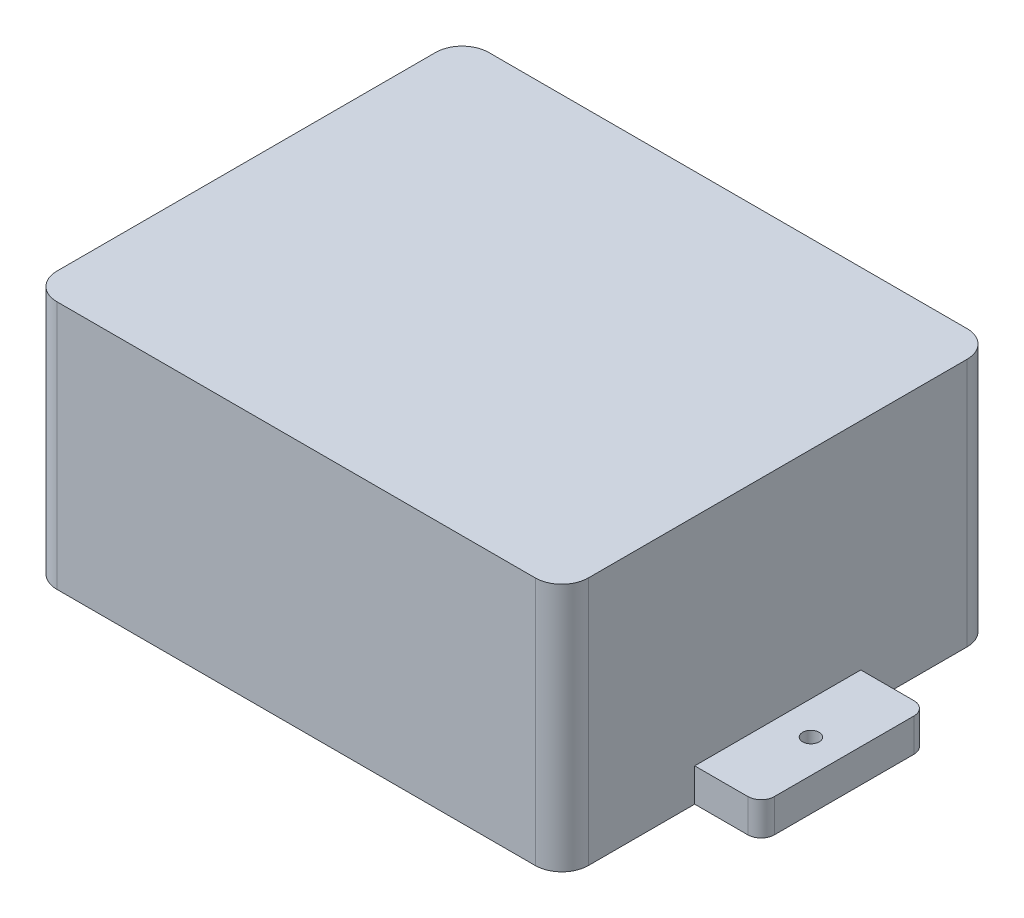
SolidWorks part; units mm, degrees
ref_plane "Front Plane" through (0, 0, 0) normal (0, 0, 1) x (1, 0, 0)
ref_plane "Top Plane" through (0, 0, 0) normal (0, 1, 0) x (1, 0, 0)
ref_plane "Right Plane" through (0, 0, 0) normal (1, 0, 0) x (0, 0, -1)
sketch "Sketch2" plane through (0, 0, 0) normal (0, 1, 0) x (1, 0, 0)
  line L0 (-50.8, 0) -> (50.8, 0) construction
  line L1 (0, -41.275) -> (0, 41.275) construction
  line L3 (-50.8, 41.275) -> (50.8, 41.275)
  line L4 (-50.8, 41.275) -> (-50.8, -41.275)
  line L5 (-50.8, -41.275) -> (50.8, -41.275)
  line L6 (50.8, 41.275) -> (50.8, -41.275)
  point P4 (0, 0)
  point P8 (0, 0)
  dimension "D1" = 82.55
  dimension "D2" = 101.6
  dimension "D3" = 50.8
  dimension "D4" = 41.275
extrude "Boss-Extrude1" add sketch "Sketch2" along normal blind 47.625 contours L4 L5 L6 L3
fillet "Fillet1" radius 5.08 4 edges at (50.8, 23.8125, 41.275) (50.8, 23.8125, -41.275) (-50.8, 23.8125, 41.275) (-50.8, 23.8125, -41.275)
sketch "Sketch3" plane through (0, 0, 0) normal (0, 1, 0) x (1, 0, 0)
  line L0 (50.8, -15.875) -> (63.5, -15.875)
  line L1 (50.8, 36.195) -> (50.8, -36.195) construction
  line L2 (50.8, 15.875) -> (63.5, 15.875)
  line L3 (-45.72, -41.275) -> (45.72, -41.275) construction
  line L4 (-45.72, 41.275) -> (45.72, 41.275) construction
  line L5 (63.5, 15.875) -> (63.5, -15.875)
  line L6 (50.8, 15.875) -> (50.8, -15.875)
  dimension "D1" = 25.4
  dimension "D2" = 25.4
  dimension "D3" = 12.7
sketch "Sketch4" plane through (0, 0, 0) normal (0, 1, 0) x (1, 0, 0)
  line L0 (-50.8, -15.875) -> (-63.5, -15.875)
  line L1 (-50.8, 36.195) -> (-50.8, -36.195) construction
  line L2 (-50.8, 15.875) -> (-63.5, 15.875)
  line L3 (-45.72, 41.275) -> (45.72, 41.275) construction
  line L4 (-45.72, -41.275) -> (45.72, -41.275) construction
  line L5 (-63.5, 15.875) -> (-63.5, -15.875)
  line L6 (-50.8, 15.875) -> (-50.8, -15.875)
  dimension "D1" = 25.4
  dimension "D2" = 25.4
  dimension "D3" = 12.7
extrude "Boss-Extrude2" add sketch "Sketch4" along normal blind 6.35 contours L5 L0 L6 L2
extrude "Boss-Extrude3" add sketch "Sketch3" along normal blind 6.35
fillet "Fillet2" radius 2.54 4 edges at (-63.5, 3.175, 15.875) (-63.5, 3.175, -15.875) (63.5, 3.175, -15.875) (63.5, 3.175, 15.875)
sketch "Sketch5" plane through (0, 0, 0) normal (0, 1, 0) x (1, 0, 0)
  line L0 (15.875, 41.275) -> (15.875, 53.975)
  line L1 (-45.72, 41.275) -> (45.72, 41.275) construction
  line L2 (-15.875, 41.275) -> (-15.875, 53.975)
  line L3 (-50.8, 36.195) -> (-50.8, -36.195) construction
  line L4 (50.8, 36.195) -> (50.8, -36.195) construction
  line L5 (-15.875, 53.975) -> (15.875, 53.975)
  line L6 (-15.875, 41.275) -> (15.875, 41.275)
  dimension "D1" = 34.925
  dimension "D2" = 34.925
  dimension "D3" = 12.7
extrude "Boss-Extrude4" add sketch "Sketch5" along normal blind 6.35 contours L0 L5 L2 L6
fillet "Fillet3" radius 2.54 2 edges at (-15.875, 3.175, -53.975) (15.875, 3.175, -53.975)
sketch "Sketch6" plane through (0, 6.35, 0) normal (0, 1, 0) x (1, 0, 0)
  line L0 (0, 53.975) -> (0, 41.275) construction
  line L1 (-13.335, 53.975) -> (13.335, 53.975) construction
  line L2 (-45.72, 41.275) -> (45.72, 41.275) construction
  line L3 (-15.875, 47.625) -> (15.875, 47.625) construction
  line L4 (15.875, 41.275) -> (15.875, 51.435) construction
  circle A0 centre (0, 47.625) radius 1.5875
  point P11 (0, 47.625)
  dimension "D1" = 3.175
extrude "Cut-Extrude1" cut sketch "Sketch6" against normal blind 9.398
sketch "Sketch7" plane through (0, 6.35, 0) normal (0, 1, 0) x (1, 0, 0)
  line L0 (-63.5, 0) -> (-50.8, 0) construction
  line L1 (-63.5, 13.335) -> (-63.5, -13.335) construction
  line L2 (-50.8, 36.195) -> (-50.8, -36.195) construction
  line L3 (-57.15, -15.875) -> (-57.15, 15.875) construction
  line L4 (-50.8, 15.875) -> (-60.96, 15.875) construction
  circle A0 centre (-57.15, 0) radius 1.5875
  point P11 (-57.15, 0)
  dimension "D1" = 3.175
extrude "Cut-Extrude2" cut sketch "Sketch7" against normal blind 9.398
sketch "Sketch8" plane through (0, 6.35, 0) normal (0, 1, 0) x (1, 0, 0)
  line L0 (63.5, 0) -> (50.8, 0) construction
  line L1 (63.5, -13.335) -> (63.5, 13.335) construction
  line L2 (50.8, 15.875) -> (50.8, -15.875) construction
  line L3 (57.15, -15.875) -> (57.15, 15.875) construction
  line L4 (60.96, 15.875) -> (50.8, 15.875) construction
  circle A0 centre (57.15, 0) radius 1.5875
  point P11 (57.15, 0)
  dimension "D1" = 3.175
extrude "Cut-Extrude3" cut sketch "Sketch8" against normal blind 9.398 contours A0
sketch "Sketch9" plane through (0, 47.625, 0) normal (0, 1, 0) x (1, 0, 0)
  line L0 (-50.8, 0) -> (50.8, 0) construction
  line L1 (50.8, 36.195) -> (50.8, -36.195) construction
  line L2 (0, 41.275) -> (0, -41.275) construction
  line L3 (-45.72, -41.275) -> (45.72, -41.275) construction
  text T0 "ARDUINO" font "Century Schoolbook" height 8.89
  point P6 (0, 0)
  point P12 (0, 0)
extrude "Cut-Extrude4" [suppressed] cut sketch "Sketch9" against normal blind 3.81
